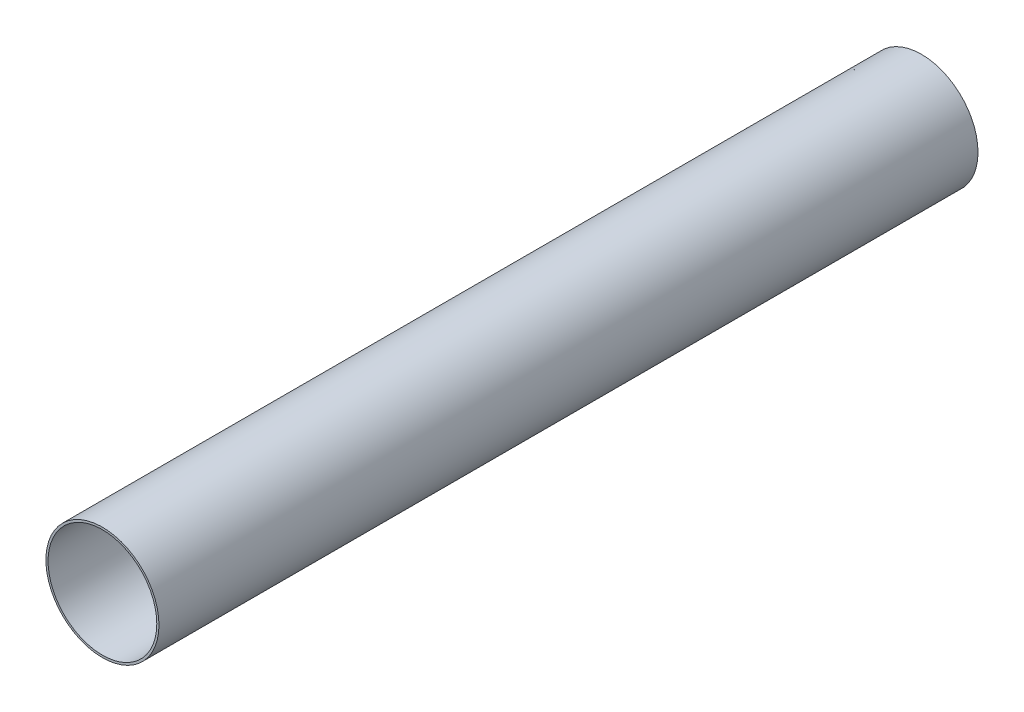
SolidWorks part; units mm, degrees
ref_plane "Front Plane" through (0, 0, 0) normal (0, 0, 1) x (1, 0, 0)
ref_plane "Top Plane" through (0, 0, 0) normal (0, 1, 0) x (1, 0, 0)
ref_plane "Right Plane" through (0, 0, 0) normal (1, 0, 0) x (0, 0, -1)
sketch "Sketch1" plane through (0, 0, 0) normal (0, 0, 1) x (1, 0, 0)
  circle A0 centre (0, 0) radius 75
  circle A1 centre (0, 0) radius 78
  dimension "D1" = 3
extrude "Boss-Extrude1" add sketch "Sketch1" against normal up to surface (1130 mm away)
